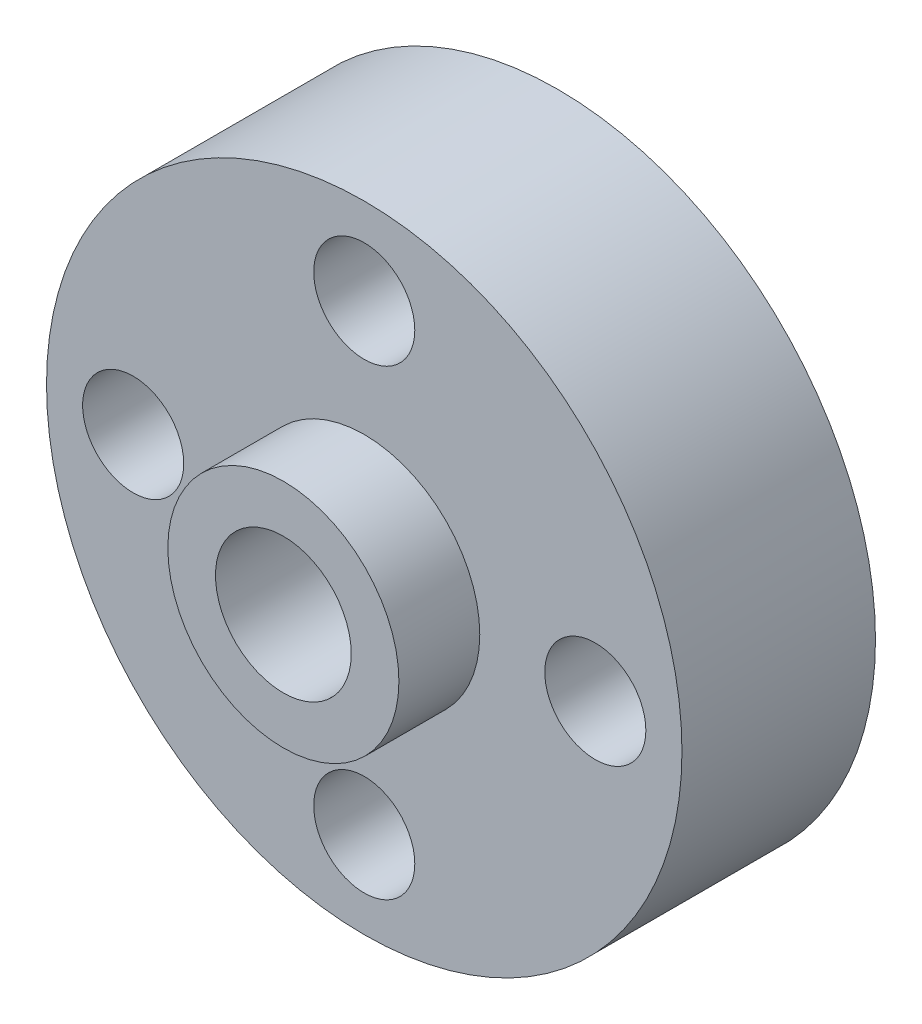
SolidWorks part; units mm, degrees
ref_plane "정면" through (0, 0, 0) normal (0, 0, 1) x (1, 0, 0)
ref_plane "윗면" through (0, 0, 0) normal (0, 1, 0) x (1, 0, 0)
ref_plane "우측면" through (0, 0, 0) normal (1, 0, 0) x (0, 0, -1)
sketch "스케치1" plane through (0, 0, 0) normal (0, 0, 1) x (1, 0, 0)
  circle A0 centre (0, 0) radius 11
  circle A1 centre (0, 8) radius 1.75
  circle A2 centre (8, 0) radius 1.75
  circle A3 centre (0, -8) radius 1.75
  circle A4 centre (-8, 0) radius 1.75
  point P14 (0, 0)
  dimension "D1" = 22
  dimension "D2" = 3.5
  dimension "D3" = 8
  dimension "D4" = 4
extrude "보스-돌출1" add sketch "스케치1" along normal blind 6.7
sketch "스케치2" plane through (0, 0, 6.7) normal (0, 0, 1) x (1, 0, 0)
  circle A0 centre (0, 0) radius 4
  circle A1 centre (0, 0) radius 2.35
  dimension "D1" = 4.7
  dimension "D2" = 8
extrude "보스-돌출2" add sketch "스케치2" along normal blind 2.8
extrude "컷-돌출1" cut sketch "스케치2<2>" against normal through all contours A1
sketch "스케치2<2>" plane through (0, 0, 6.7) normal (0, 0, 1) x (1, 0, 0) same geometry as "스케치2"
